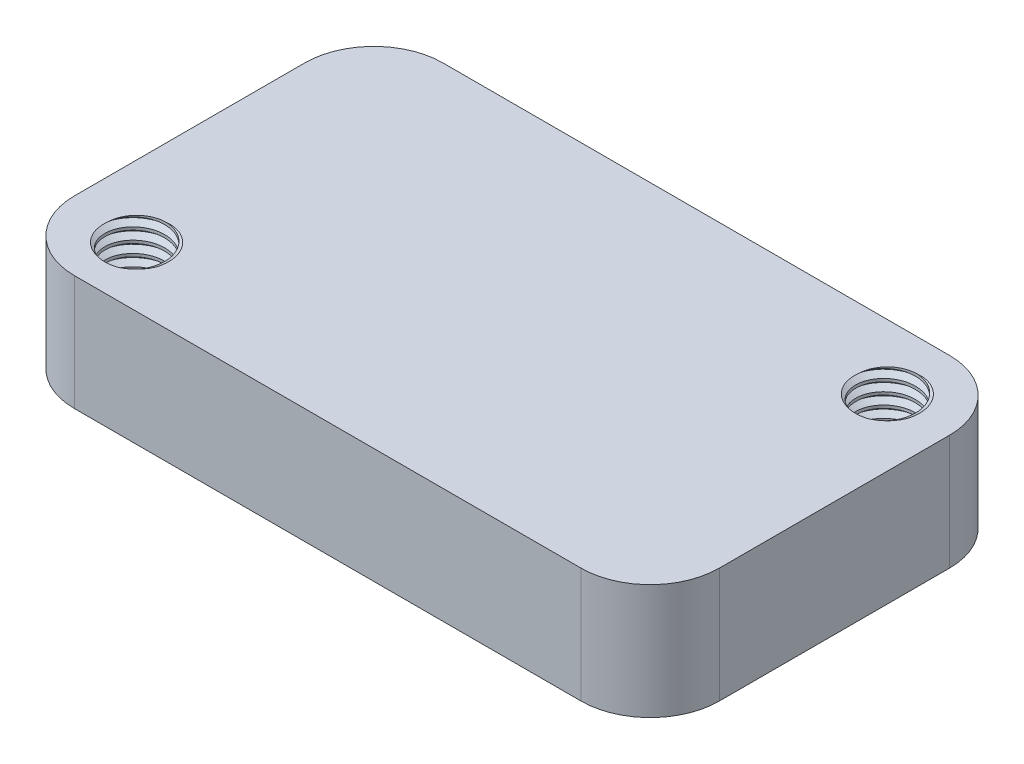
SolidWorks part; units mm, degrees
ref_plane "Front Plane" through (0, 0, 0) normal (0, 0, 1) x (1, 0, 0)
ref_plane "Top Plane" through (0, 0, 0) normal (0, 1, 0) x (1, 0, 0)
ref_plane "Right Plane" through (0, 0, 0) normal (1, 0, 0) x (0, 0, -1)
sketch "Sketch1" plane through (0, 0, 0) normal (0, 1, 0) x (1, 0, 0)
  line L1 (-14, 8) -> (14, 8)
  line L2 (-14, 8) -> (-14, -8)
  line L3 (-14, -8) -> (14, -8)
  line L4 (14, 8) -> (14, -8)
  line L5 (-14, 8) -> (14, -8) construction
  line L6 (-14, -8) -> (14, 8) construction
  line L7 (-11, -5.3) -> (11, -5.3)
  line L8 (-11, -5.3) -> (-11, 5.3)
  line L9 (-11, 5.3) -> (11, 5.3)
  line L10 (11, -5.3) -> (11, 5.3)
  line L11 (-11, -5.3) -> (11, 5.3) construction
  line L12 (-11, 5.3) -> (11, -5.3) construction
  circle A1 centre (11, 5.3) radius 1.3
  circle A3 centre (-11, -5.3) radius 1.3
  point P0 (0, 0)
  point P6 (0, 0)
  dimension "D1" = 28
  dimension "D2" = 16
  dimension "D3" = 22
  dimension "D4" = 10.6
extrude "Boss-Extrude1" add sketch "Sketch1" along normal blind 5 contours L4 L1 L2 L3 A3 L8 L9 A1 L10 L7 | A3 L7 L10 A1 L9 L8 region at (0, 0, -7.6775) region at (0, 0, 0)
fillet "Fillet1" radius 3 4 edges at (14, 2.5, 8) (14, 2.5, -8) (-14, 2.5, -8) (-14, 2.5, 8)
thread "Thread1" pitch 0.5 method cut profile "Thread Profile1" start angle 0, offset 1, length 10, pitch 0.5, diameter 2.6
ref_plane "Plane1" through (-12.3, 6, 5.3) normal (0, 0, 1) x (-1, 0, 0)
sketch "Thread Profile1" plane through (-12.3, 6, 5.3) normal (0, 0, 1) x (-1, 0, 0)
  line L0 (0, 0) -> (0, 0.5) construction
  line L1 (0, 0) -> (0.2706, 0.1562)
  line L2 (0.2706, 0.1562) -> (0.2706, 0.2187)
  line L3 (0.2706, 0.2187) -> (0, 0.375)
  line L4 (0.2706, 0.1875) -> (0, 0.1875) construction
  line L11 (0, 0) -> (0, 0.375)
  point P2 (0, 0)
  dimension "Pitch" = 0.5
  dimension "Profile_Angle" = 60
  dimension "Profile_Land" = 0.0625
  dimension "Profile_Height" = 0.2706
thread "Thread2" pitch 0.5 method cut profile "Thread Profile2" start angle 0, offset 1, length 10, pitch 0.5, diameter 2.6
ref_plane "Plane2" through (9.7, 6, -5.3) normal (0, 0, 1) x (-1, 0, 0)
sketch "Thread Profile2" plane through (9.7, 6, -5.3) normal (0, 0, 1) x (-1, 0, 0)
  line L0 (0, 0) -> (0, 0.5) construction
  line L1 (0, 0) -> (0.2706, 0.1562)
  line L2 (0.2706, 0.1562) -> (0.2706, 0.2187)
  line L3 (0.2706, 0.2187) -> (0, 0.375)
  line L4 (0.2706, 0.1875) -> (0, 0.1875) construction
  line L11 (0, 0) -> (0, 0.375)
  point P2 (0, 0)
  dimension "Pitch" = 0.5
  dimension "Profile_Angle" = 60
  dimension "Profile_Land" = 0.0625
  dimension "Profile_Height" = 0.2706
